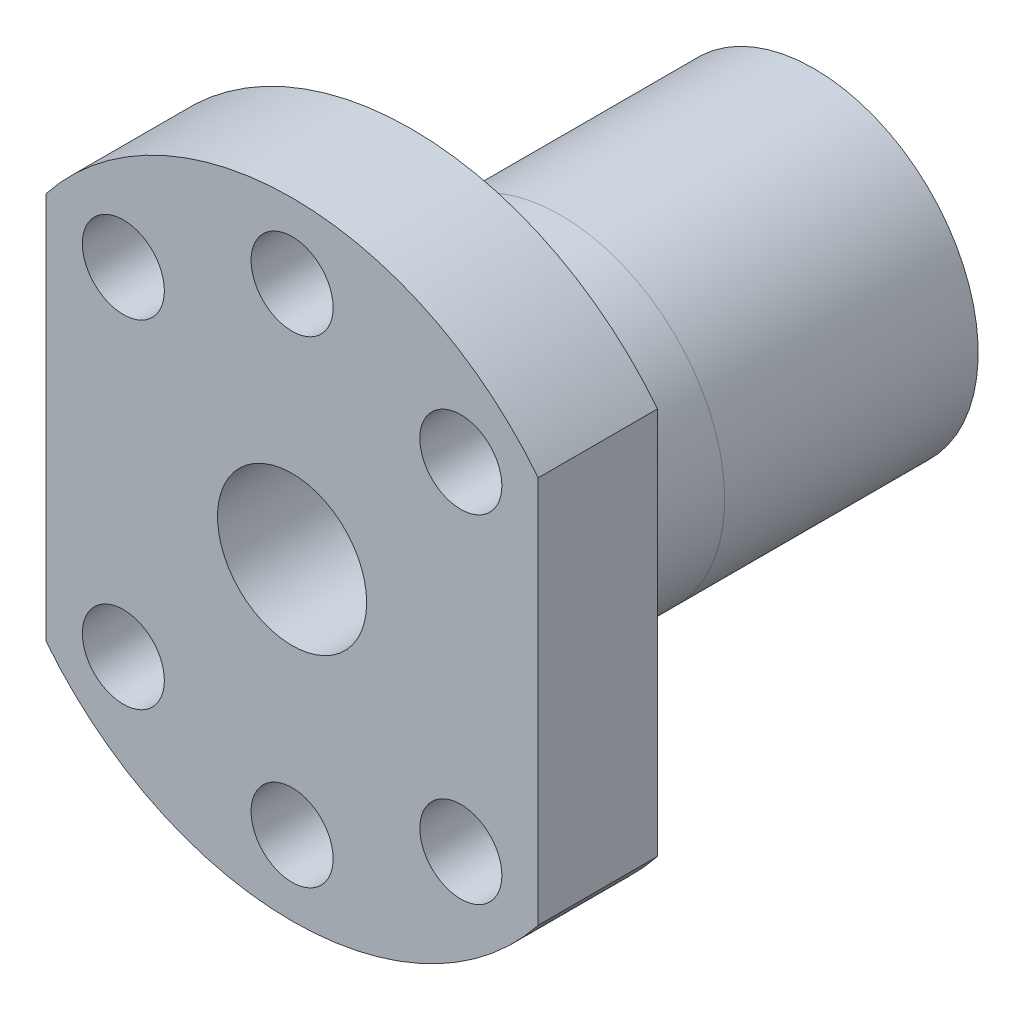
SolidWorks part; units mm, degrees
ref_plane "前视基准面" through (0, 0, 0) normal (0, 0, 1) x (1, 0, 0)
ref_plane "上视基准面" through (0, 0, 0) normal (0, 1, 0) x (1, 0, 0)
ref_plane "右视基准面" through (0, 0, 0) normal (1, 0, 0) x (0, 0, -1)
sketch "草图1" plane through (0, 0, 0) normal (0, 0, 1) x (1, 0, 0)
  line L0 (0, 0) -> (16, 0) construction
  line L1 (0, 0) -> (0, -16) construction
  line L2 (0, 0) -> (11.3137, 11.3137) construction
  line L3 (0, 0) -> (-11.3137, 11.3137) construction
  line L4 (0, 0) -> (6.1229, -14.7821) construction
  line L5 (-8, 13.8564) -> (0, 0) construction
  line L6 (0, 0) -> (8, 13.8564) construction
  line L7 (-16.5, -12.9904) -> (-16.5, 12.9904)
  line L8 (16.5, 12.9904) -> (16.5, -12.9904)
  line L9 (0, 0) -> (1.8478, 0.7654)
  line L10 (1.8478, 0.7654) -> (9.8841, -18.6361)
  line L11 (9.8841, -18.6361) -> (8.0364, -19.4015)
  line L12 (1.4782, 0.6123) -> (7.2185, -13.2459)
  line L13 (7.2185, -13.2459) -> (7.588, -13.0928)
  line L14 (-12, -17.2337) -> (-12, 17.2337)
  line L15 (12, 17.2337) -> (12, -17.2337)
  circle A0 centre (0, 0) radius 21
  circle A1 centre (0, 0) radius 16 construction
  circle A2 centre (11.3137, 11.3137) radius 2.75
  circle A3 centre (-11.3137, 11.3137) radius 2.75
  circle A4 centre (0, 16) radius 2.75
  circle A5 centre (-8, 13.8564) radius 2.75
  circle A6 centre (8, 13.8564) radius 2.75
  circle A7 centre (0, 0) radius 5
  point P21 (0, 21)
  dimension "D1" = 90
  dimension "D6" = 42
  dimension "(D4)" = 32
  dimension "D5" = 5.5
  dimension "D2" = 3.2
  dimension "(d)" = 10
  dimension "JD" = 22.5
  dimension "D3" = 60
  dimension "D4" = 6
  dimension "L5" = 33
  dimension "Q" = 4
  dimension "L6" = 24
sketch "草图2" plane through (0, 0, 0) normal (1, 0, 0) x (0, 0, -1)
  line L0 (-4, 0) -> (31, 0) construction
  line L1 (-4, 0) -> (-4, 21)
  line L2 (-4, 21) -> (4, 21)
  line L3 (4, 21) -> (4, 11)
  line L4 (4, 11) -> (31, 11)
  line L5 (31, 11) -> (31, 0)
  line L6 (0, 0) -> (0, 21) construction
  line L7 (14, 11) -> (14, 0)
  line L8 (-75, 0) -> (75, 0) construction
  line L9 (75, 0) -> (-40, 0)
  dimension "D1" = 22
  dimension "L1" = 35
  dimension "L2" = 8
  dimension "L7" = 10
  dimension "ZL" = 150
  dimension "D3" = 115
sketch "草图3" plane through (0, 0, 0) normal (1, 0, 0) x (0, 0, -1)
  line L0 (-4, 0) -> (-4, 21) construction
  line L1 (-4, 21) -> (4, 21) construction
  line L2 (4, 21) -> (4, 11) construction
  line L3 (4, 11) -> (31, 11) construction
  line L4 (31, 11) -> (31, 0) construction
  line L5 (-4, 0) -> (-4, 21)
  line L6 (-4, 21) -> (4, 21)
  line L7 (4, 21) -> (4, 11)
  line L8 (4, 11) -> (31, 11)
  line L9 (31, 11) -> (31, 0)
  line L10 (-4, 0) -> (31, 0)
revolve "旋转1" add sketch "草图3" angle 360 about L10
sketch "草图13" plane through (0, 0, 0) normal (0, 0, 1) x (1, 0, 0)
  line L0 (-16.5, -12.9904) -> (-16.5, 12.9904) construction
  line L1 (16.5, 12.9904) -> (16.5, -12.9904) construction
  line L2 (-16.5, -12.9904) -> (-16.5, 12.9904)
  line L3 (16.5, 12.9904) -> (16.5, -12.9904)
  circle A0 centre (0, 0) radius 21 construction
  arc A1 (-16.5, 12.9904) -> (-16.5, -12.9904) centre (0, 0) ccw
  arc A2 (16.5, -12.9904) -> (16.5, 12.9904) centre (0, 0) ccw
extrude "切除-拉伸7" cut sketch "草图13" along normal up to vertex (4 mm away) from vertex up to point (0, 21, 4) starting at point (0, 21, -4)
sketch "草图5" plane through (0, 0, 0) normal (0, 0, 1) x (1, 0, 0)
  circle A0 centre (-11.3137, 11.3137) radius 2.75 construction
  circle A1 centre (11.3137, 11.3137) radius 2.75 construction
  circle A2 centre (-11.3137, 11.3137) radius 2.75
  circle A3 centre (11.3137, 11.3137) radius 2.75
extrude "切除-拉伸2" cut sketch "草图5" along normal up to vertex (4 mm away) from vertex up to point (0, 21, 4) starting at point (0, 21, -4)
mirror "镜向1" about plane through (0, 0, 0) normal (0, 1, 0) of "切除-拉伸2"
sketch "草图6" plane through (0, 0, 0) normal (0, 0, 1) x (1, 0, 0)
  circle A0 centre (0, 16) radius 2.75 construction
  circle A1 centre (0, 16) radius 2.75
extrude "切除-拉伸3" cut sketch "草图6" along normal up to vertex (4 mm away) from vertex up to point (0, 21, 4) starting at point (0, 21, -4)
mirror "镜向2" about plane through (0, 0, 0) normal (0, 1, 0) of "切除-拉伸3"
sketch "草图7" [suppressed] plane through (0, 0, 0) normal (0, 0, 1) x (1, 0, 0)
  circle A0 centre (-5.75, 9.9593) radius 1.7 construction
  circle A1 centre (5.75, 9.9593) radius 1.7 construction
  circle A2 centre (-5.75, 9.9593) radius 1.7
  circle A3 centre (5.75, 9.9593) radius 1.7
extrude "切除-拉伸4" [suppressed] cut sketch "草图7" along normal up to vertex from vertex up to point (0, 21, 4) starting at point (0, 21, -4)
mirror "镜向3" [suppressed] about plane through (0, 0, 0) normal (0, 1, 0)
sketch "草图14" [suppressed] plane through (0, 0, 0) normal (0, 0, 1) x (1, 0, 0)
  line L0 (-10, -11.8427) -> (-10, 11.8427) construction
  line L1 (10, 11.8427) -> (10, -11.8427) construction
  line L2 (-10, -11.8427) -> (-10, 11.8427)
  line L3 (10, 11.8427) -> (10, -11.8427)
  circle A0 centre (0, 0) radius 15.5 construction
  arc A1 (-10, 11.8427) -> (-10, -11.8427) centre (0, 0) ccw
  arc A2 (10, -11.8427) -> (10, 11.8427) centre (0, 0) ccw
extrude "切除-拉伸8" [suppressed] cut sketch "草图14" along normal up to vertex from vertex up to point (0, 21, 4) starting at point (0, 21, -4)
sketch "草图8" plane through (0, 0, 0) normal (0, 0, 1) x (1, 0, 0)
  circle A0 centre (0, 0) radius 5 construction
  circle A1 centre (0, 0) radius 5
extrude "切除-拉伸5" cut sketch "草图8" against normal through all and the other way through all
cosmetic thread "装饰螺纹线2" parameters "D2"=10.1
sketch "草图11" plane through (0, 0, 0) normal (1, 0, 0) x (0, 0, -1)
  line L0 (14, 11) -> (14, -11)
  line L1 (4, -11) -> (31, -11) construction
split line "分割线1"
sketch "草图10" plane through (0, 0, 0) normal (0, 0, 1) x (1, 0, 0)
  circle A0 centre (0, 0) radius 5 construction
  circle A1 centre (0, 0) radius 5
extrude "凸台-拉伸1" add sketch "草图10" along normal up to vertex (75 mm away) from vertex separate body up to point (0, 0, 75) starting at point (0, 0, -75)
cosmetic thread "装饰螺纹线3" parameters "D2"=8.5
sketch "草图12" [suppressed] plane through (0, 0, 4) normal (0, 0, 1) x (1, 0, 0)
  circle A0 centre (16, 0) radius 2.75
  circle A1 centre (-11.3137, 11.3137) radius 2.75 construction
extrude "切除-拉伸6" [suppressed] cut sketch "草图12" against normal up to vertex up to point (0, 21, -4)
pattern_circular "阵列(圆周)1" [suppressed] count 6 over 360 of bodies 113
delete or keep bodies "实体-删除1" type delete bodies bodies 111
